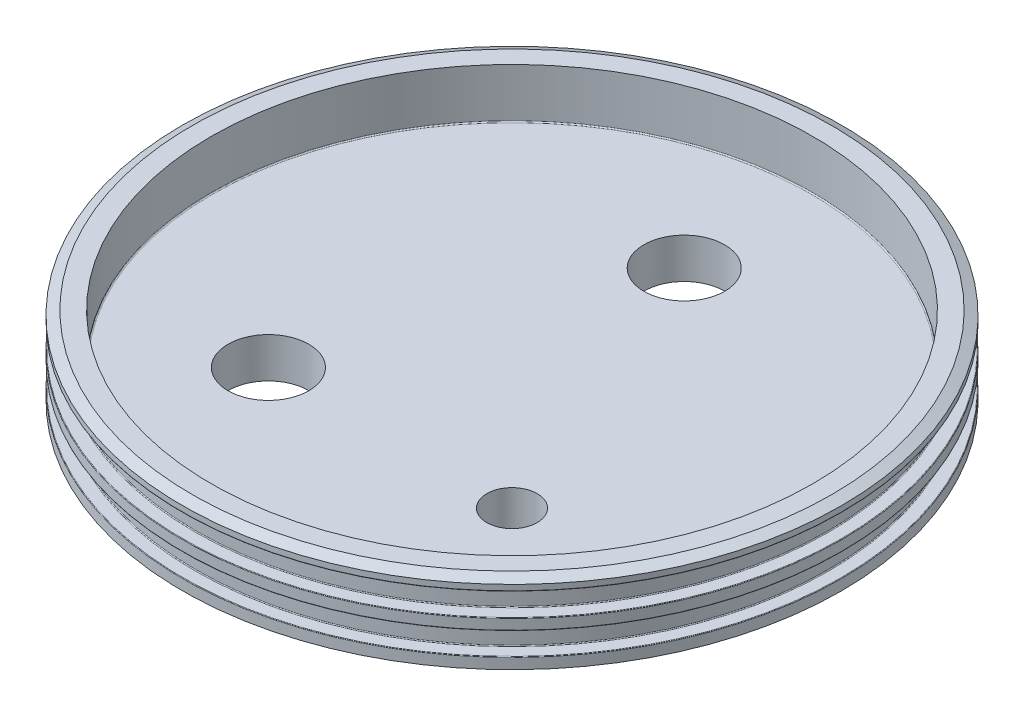
SolidWorks part; units mm, degrees
material "6061-T6 (SS)"
ref_plane "Front Plane" through (0, 0, 0) normal (0, 0, 1) x (1, 0, 0)
ref_plane "Top Plane" through (0, 0, 0) normal (0, 1, 0) x (1, 0, 0)
ref_plane "Right Plane" through (0, 0, 0) normal (1, 0, 0) x (0, 0, -1)
sketch "Sketch1" plane through (0, 0, 0) normal (0, 0, 1) x (1, 0, 0)
  line L0 (0, 48.1922) -> (0, -25.6743) construction
  line L1 (0, 0) -> (72.898, 0)
  line L2 (72.898, 0) -> (72.898, 2.4638)
  line L3 (72.898, 2.4638) -> (69.977, 2.4638)
  line L4 (69.977, 2.4638) -> (69.977, 7.4422)
  line L5 (69.977, 7.4422) -> (72.898, 7.4422)
  line L6 (72.898, 7.4422) -> (72.898, 9.906)
  line L7 (72.898, 9.906) -> (69.977, 9.906)
  line L8 (66.548, 17.3482) -> (66.548, 6.35)
  line L9 (66.548, 6.35) -> (0, 6.35)
  line L10 (0, 6.35) -> (0, 0)
  line L11 (69.977, 9.906) -> (69.977, 14.986)
  line L12 (69.977, 14.986) -> (72.898, 14.986)
  line L13 (72.898, 14.986) -> (72.898, 17.3482)
  line L14 (72.898, 17.3482) -> (66.548, 17.3482)
  dimension "D1" = 145.796
  dimension "D2" = 4.9784
  dimension "D3" = 2.921
  dimension "D4" = 9.906
  dimension "D5" = 6.35
  dimension "D6" = 6.35
  dimension "D7" = 5.08
  dimension "D8" = 9.906
revolve "Revolve1" add sketch "Sketch1" angle 360 about L0
sketch "Sketch6" plane through (0, 0, 0) normal (0, -1, 0) x (1, 0, 0)
  circle A0 centre (0, 0) radius 66.04
  dimension "D1" = 132.08
extrude "Boss-Extrude1" add sketch "Sketch6" along normal blind 2.54
fillet "CNC ID Fillet" radius 0.1778 5 edges at (-69.977, 7.4422, 0) (-69.977, 2.4638, 0) (66.04, 0, 0) (-69.977, 14.986, 0) (-69.977, 9.906, 0)
fillet "CNC OD Fillet" radius 0.127 5 edges at (-72.898, 7.4422, 0) (-72.898, 2.4638, 0) (-72.898, 9.906, 0) (-72.898, 14.986, 0) (66.04, -2.54, 0)
chamfer "CNC Chamfers" distance 1.016 angle 65 1 edges at (-72.898, 17.3482, 0) first distance on face at (-72.898, 15.113, 0)
fillet "CNC Bore Fillet" radius 0.254 1 edges at (-66.548, 6.35, 0)
hole_wizard "Pipe Tap Drill for 1/2 Tap - Fill Valve" positions "Sketch13" profile "Sketch14" hole size "1/2" standard "ANSI Inch" end condition through all
sketch "Sketch13" plane through (0, -2.54, 0) normal (0, -1, 0) x (-1, 0, 0)
  point P4 (0, 38.1)
  dimension "D1" = 38.1
sketch "Sketch14" plane through (0, -2.54, -38.1) normal (1, 0, 0) x (0, 0, -1)
  line L0 (0, 0) -> (0, 19.8882)
  line L1 (0, 19.8882) -> (8.9281, 19.8882)
  line L2 (8.9281, 19.8882) -> (8.9281, 0)
  line L5 (8.9281, 0) -> (0, 0)
  line L11 (0, -6.35) -> (0, 107.95) construction
  dimension "Thru Hole Dia." = 17.8562
  dimension "Thru Hole Depth" = 19.8882
hole_wizard "Pipe Tap Drill for 1/4 Tap - Solenoid Valve" positions "Sketch15" profile "Sketch16" hole size "1/4" standard "ANSI Inch" end condition through all
sketch "Sketch15" plane through (0, -2.54, 0) normal (0, -1, 0) x (-1, 0, 0)
  line L0 (-26.9408, -26.9408) -> (-4.9437, -26.9408) construction
  line L2 (-26.9408, -26.9408) -> (0, 0) construction
  point P4 (-26.9408, -26.9408)
  dimension "D1" = 45
  dimension "D2" = 38.1
sketch "Sketch16" plane through (26.9408, -2.54, 26.9408) normal (1, 0, 0) x (0, 0, -1)
  line L0 (0, 0) -> (0, 19.8882)
  line L1 (0, 19.8882) -> (5.5626, 19.8882)
  line L2 (5.5626, 19.8882) -> (5.5626, 0)
  line L5 (5.5626, 0) -> (0, 0)
  line L11 (0, -6.35) -> (0, 107.95) construction
  dimension "Thru Hole Dia." = 11.1252
  dimension "Thru Hole Depth" = 19.8882
hole_wizard "Pipe Tap Drill for 1/2 Tap - Cryo Valve" positions "Sketch17" profile "Sketch18" hole size "1/2" standard "ANSI Inch" end condition through all
sketch "Sketch17" plane through (0, -2.54, 0) normal (0, -1, 0) x (-1, 0, 0)
  line L0 (26.9408, -26.9408) -> (11.2265, -26.9408) construction
  line L2 (26.9408, -26.9408) -> (0, 0) construction
  point P4 (26.9408, -26.9408)
  dimension "D1" = 45
  dimension "D2" = 38.1
sketch "Sketch18" plane through (-26.9408, -2.54, 26.9408) normal (1, 0, 0) x (0, 0, -1)
  line L0 (0, 0) -> (0, 19.8882)
  line L1 (0, 19.8882) -> (8.9281, 19.8882)
  line L2 (8.9281, 19.8882) -> (8.9281, 0)
  line L5 (8.9281, 0) -> (0, 0)
  line L11 (0, -6.35) -> (0, 107.95) construction
  dimension "Thru Hole Dia." = 17.8562
  dimension "Thru Hole Depth" = 19.8882
